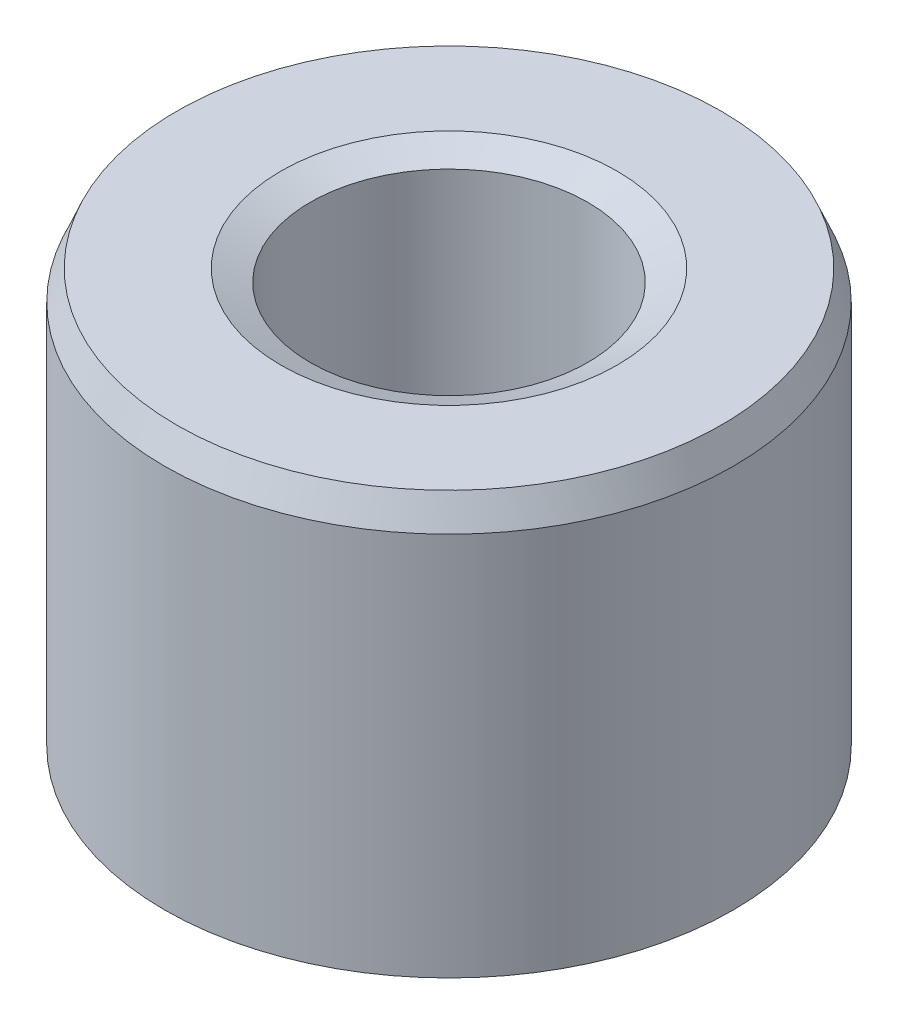
SolidWorks part; units mm, degrees
ref_plane "Front Plane" through (0, 0, 0) normal (0, 0, 1) x (1, 0, 0)
ref_plane "Top Plane" through (0, 0, 0) normal (0, 1, 0) x (1, 0, 0)
ref_plane "Right Plane" through (0, 0, 0) normal (1, 0, 0) x (0, 0, -1)
sketch "Sketch1" plane through (0, 0, 0) normal (0, 1, 0) x (1, 0, 0)
  circle A0 centre (0, 0) radius 32.5
  dimension "SLEEVE_OD" = 65
extrude "Boss-Extrude1" add sketch "Sketch1" along normal blind 48.6723
sketch "Sketch2" plane through (0, 0, 0) normal (0, 1, 0) x (1, 0, 0)
  circle A0 centre (0, 0) radius 15.8597
  dimension "BORE_D" = 31.7193
extrude "Cut-Extrude1" cut sketch "Sketch2" along normal through all
chamfer "Chamfer1" distance 3.3498 angle 22.818 4 edges at (0, 48.6723, 15.8597) (0, 0, 15.8597) (0, 0, 32.5) (0, 48.6723, 32.5) first distance on face at (0, 48.6723, 15.8597) first distance on face at (0, 0, 15.8597) first distance on face at (0, 48.6723, 32.5)
